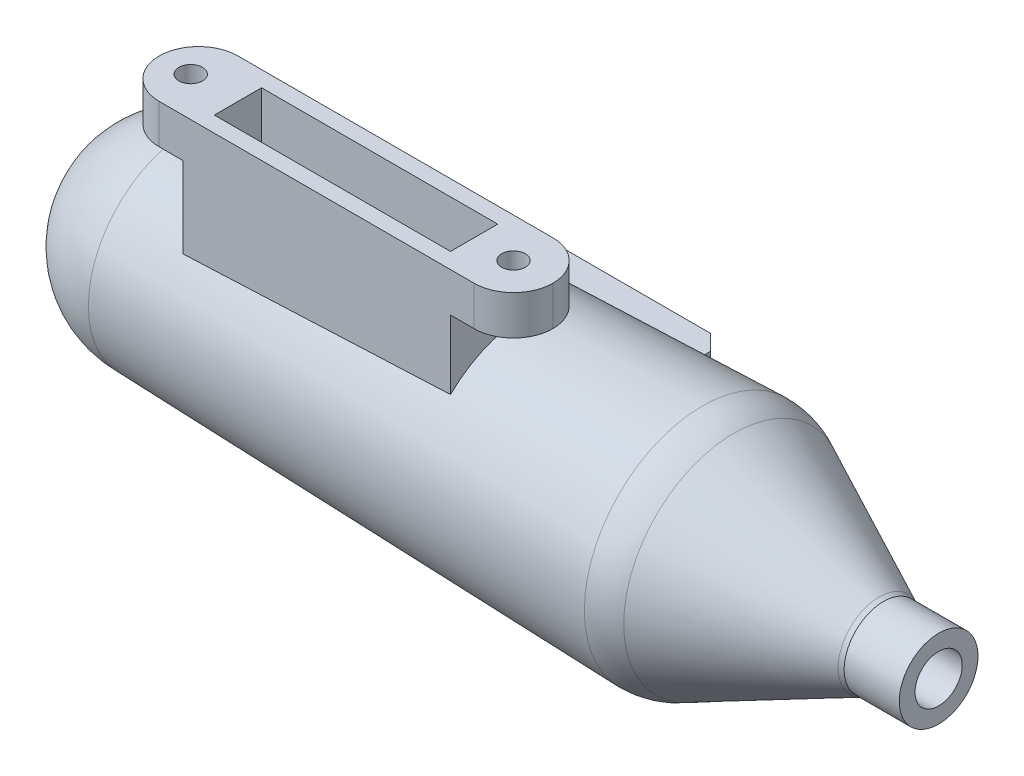
SolidWorks part; units mm, degrees
material "Plain Carbon Steel"
ref_plane "Front Plane" through (0, 0, 0) normal (0, 0, 1) x (1, 0, 0)
ref_plane "Top Plane" through (0, 0, 0) normal (0, 1, 0) x (1, 0, 0)
ref_plane "Right Plane" through (0, 0, 0) normal (1, 0, 0) x (0, 0, -1)
sketch "Sketch1" plane through (0, 0, 0) normal (0, 0, 1) x (1, 0, 0)
  line L0 (54, 0) -> (-54, 0) construction
  line L1 (24, 0) -> (24, 10.9695) construction
  line L2 (24, 0) -> (24, 15) construction
  line L3 (-41, 0) -> (-41, 13) construction
  line L4 (-41, 13) -> (24, 15)
  line L5 (54, 3) -> (54, 5)
  line L6 (54, 5) -> (47, 5)
  line L7 (46.4463, 5.2149) -> (28, 14)
  line L8 (45.5863, 3.4092) -> (27.0809, 12.2225)
  line L9 (-40.9705, 11) -> (24.0453, 13.0004)
  line L10 (52, 3) -> (54, 3)
  line L11 (52, 3) -> (47, 3)
  line L12 (-54, 0) -> (-52, 0)
  line L14 (54, 0) -> (54, 5) construction
  line L15 (52, 0) -> (52, 3) construction
  arc A0 (-41, 13) -> (-54, 0) centre (-41, 0) ccw
  arc A1 (24, 15) -> (28, 14) centre (24.1252, 7.001) cw
  arc A2 (46.4463, 5.2149) -> (47, 5) centre (48.1662, 8.8262) ccw
  arc A3 (24.0453, 13.0004) -> (27.0809, 12.2225) centre (24.1252, 7.001) cw
  arc A4 (-40.9705, 11) -> (-52, 0) centre (-41, 0) ccw
  arc A5 (45.5863, 3.4092) -> (47, 3) centre (47.3863, 6.9813) ccw
  point P4 (0, 0)
  dimension "D2" = 26
  dimension "D4" = 15
  dimension "D9" = 8
  dimension "D11" = 4
  dimension "D12" = 2
  dimension "D13" = 4
  dimension "D1" = 108
  dimension "D3" = 65
  dimension "D5" = 5
  dimension "D6" = 7
  dimension "D7" = 19
  dimension "D8" = 14
  dimension "D10" = 18.4463
revolve "Revolve1" add sketch "Sketch1" angle 360 about L0
ref_plane "Plane1" through (0, 24, 0) normal (0, 1, 0) x (1, 0, 0)
sketch "Sketch2" plane through (0, 24, 0) normal (0, 1, 0) x (1, 0, 0)
  line L0 (-16.5011, 0) -> (16.5011, 0) construction
  line L1 (-32, 0) -> (2, 0)
  line L2 (-32, 0) -> (-32, -10)
  line L3 (-32, -10) -> (2, -10)
  line L4 (2, 0) -> (2, -10)
  line L5 (-41, 13) -> (-41, -13) construction
  line L7 (-30, -2) -> (0, -2)
  line L8 (-30, -2) -> (-30, -8)
  line L9 (-30, -8) -> (0, -8)
  line L10 (0, -2) -> (0, -8)
  dimension "D1" = 34
  dimension "D2" = 10
  dimension "D3" = 9
  dimension "D4" = 6
  dimension "D5" = 2
  dimension "D6" = 2
  dimension "D7" = 2
sketch "Sketch3" plane through (0, 0, 0) normal (0, 0, 1) x (1, 0, 0)
  line L0 (-32, 24) -> (-32, 13.2769)
  line L1 (-32, 24) -> (2, 24) construction
  line L2 (24, 15) -> (-41, 13) construction
  dimension "D1" = 10.7231
extrude "Boss-Extrude1" add sketch "Sketch2" against normal up to surface (9.6769 mm away) up to face at (-41, 0, -13)
sketch "Sketch4" plane through (0, 24, 0) normal (0, 1, 0) x (1, 0, 0)
  line L0 (0, -2) -> (0, -8) construction
  line L1 (0, -8) -> (-30, -8) construction
  line L2 (-30, -8) -> (-30, -2) construction
  line L3 (0, -2) -> (-30, -2) construction
  line L4 (0, -2) -> (0, -8)
  line L5 (0, -8) -> (-30, -8)
  line L6 (-30, -8) -> (-30, -2)
  line L7 (0, -2) -> (-30, -2)
extrude "Cut-Extrude4" cut sketch "Sketch4" against normal blind 20
sketch "Sketch5" plane through (0, 24, 0) normal (0, 1, 0) x (1, 0, 0)
  line L0 (-21.4505, 0) -> (21.4505, 0) construction
  line L1 (10, -10) -> (-40, -10)
  line L2 (10, -10) -> (10, 0)
  line L3 (10, 0) -> (-40, 0)
  line L4 (-40, -10) -> (-40, 0)
  line L5 (10, -10) -> (-40, 0) construction
  line L6 (10, 0) -> (-40, -10) construction
  line L7 (-30, -8) -> (0, -8) construction
  line L8 (-30, -2) -> (-30, -8) construction
  line L9 (0, -8) -> (0, -2) construction
  line L10 (-30, -2) -> (0, -2) construction
  line L11 (0, -8) -> (0, -2)
  line L12 (-30, -8) -> (0, -8)
  line L13 (-30, -2) -> (-30, -8)
  line L14 (-30, -2) -> (0, -2)
  circle A0 centre (-36, -5) radius 1.5
  circle A1 centre (5, -5) radius 1.5
  point P0 (-15, -5)
  point P10 (-15, -8)
  point P14 (-30, -5)
  dimension "D2" = 3
  dimension "D3" = 3
  dimension "D4" = 41
  dimension "D5" = 5
  dimension "D6" = 5
  dimension "D7" = 5
  dimension "D1" = 50
extrude "Boss-Extrude2" add sketch "Sketch5" against normal blind 5
fillet "Fillet1" radius 5 4 edges at (10, 21.5, 10) (10, 21.5, 0) (-40, 21.5, 0) (-40, 21.5, 10)
ref_plane "Plane2" through (0, 0, -17) normal (0, 0, 1) x (1, 0, 0)
sketch "Sketch6" plane through (0, 0, -17) normal (0, 0, 1) x (1, 0, 0)
  line L0 (16.5011, 0) -> (-16.5011, 0) construction
  line L1 (10, 6.5) -> (-39, 6.5)
  line L2 (10, 6.5) -> (10, 5.5)
  line L3 (10, 5.5) -> (-39, 5.5)
  line L4 (-39, 6.5) -> (-39, 5.5)
  line L5 (10, 3.5) -> (-39, 3.5)
  line L6 (10, 3.5) -> (10, 2.5)
  line L7 (10, 2.5) -> (-39, 2.5)
  line L8 (-39, 3.5) -> (-39, 2.5)
  line L9 (10, 0.5) -> (-39, 0.5)
  line L10 (10, 0.5) -> (10, -0.5)
  line L11 (10, -0.5) -> (-39, -0.5)
  line L12 (-39, 0.5) -> (-39, -0.5)
  line L13 (10, -2.5) -> (-39, -2.5)
  line L14 (10, -2.5) -> (10, -3.5)
  line L15 (10, -3.5) -> (-39, -3.5)
  line L16 (-39, -2.5) -> (-39, -3.5)
  line L17 (10, -5.5) -> (-39, -5.5)
  line L18 (10, -5.5) -> (10, -6.5)
  line L19 (10, -6.5) -> (-39, -6.5)
  line L20 (-39, -5.5) -> (-39, -6.5)
  line L21 (10, 19) -> (10, 24) construction
  point P22 (-39, 6)
  dimension "D1" = 13
  dimension "D2" = 6.5
  dimension "D3" = 49
  dimension "D4" = 1
  dimension "D5" = 1
  dimension "D6" = 1
  dimension "D7" = 1
  dimension "D8" = 1
  dimension "D9" = 2
  dimension "D10" = 2
  dimension "D11" = 2
extrude "Boss-Extrude3" add sketch "Sketch6" along normal up to surface (3.9611 mm away) up to face at (-10.75, 12.3523, 5.2225)
chamfer "Chamfer1" distance 2 angle 45 7 edges at (-39, -6, -17) (-39, -3, -17) (-39, 0, -17) (-39, 3, -17) (-39, 6, -17) (10, -6, -17) (10, 6, -17)
